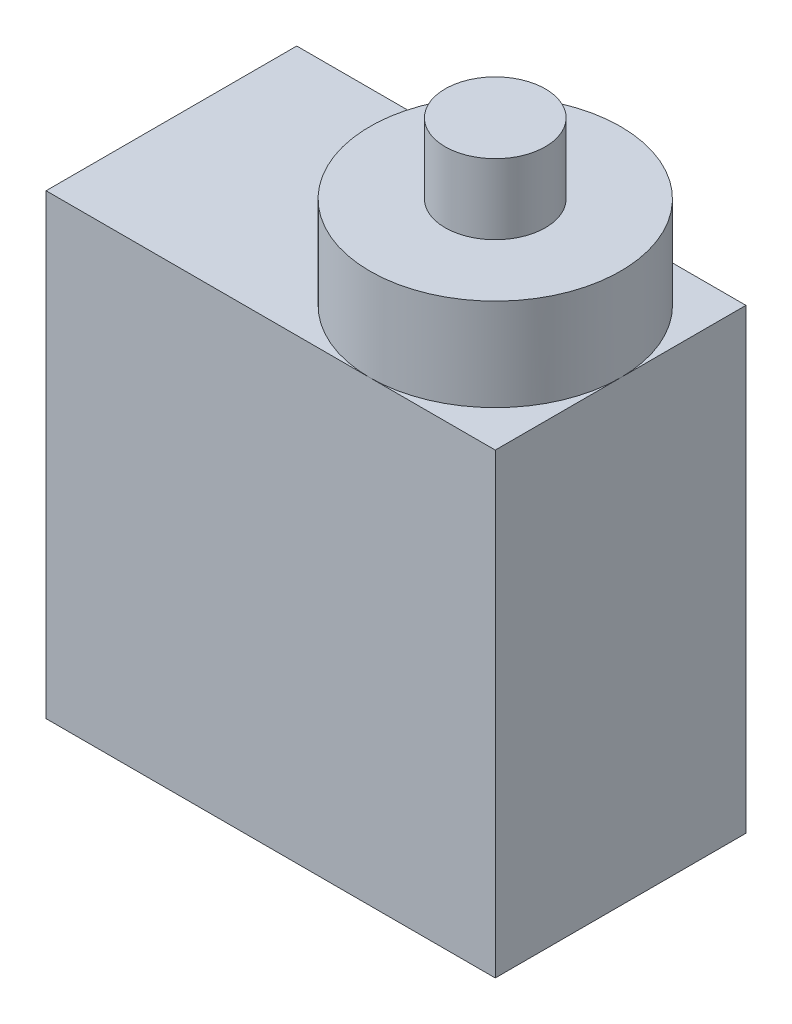
SolidWorks part; units mm, degrees
ref_plane "Front Plane" through (0, 0, 0) normal (0, 0, 1) x (1, 0, 0)
ref_plane "Top Plane" through (0, 0, 0) normal (0, 1, 0) x (1, 0, 0)
ref_plane "Right Plane" through (0, 0, 0) normal (1, 0, 0) x (0, 0, -1)
sketch "Sketch1" plane through (0, 0, 0) normal (0, 1, 0) x (1, 0, 0)
  line L1 (-11.2, 6.25) -> (11.2, 6.25)
  line L2 (-11.2, 6.25) -> (-11.2, -6.25)
  line L3 (-11.2, -6.25) -> (11.2, -6.25)
  line L4 (11.2, 6.25) -> (11.2, -6.25)
  line L5 (-11.2, 6.25) -> (11.2, -6.25) construction
  line L6 (-11.2, -6.25) -> (11.2, 6.25) construction
  point P0 (0, 0)
  dimension "D1" = 12.5
  dimension "D2" = 22.4
extrude "Boss-Extrude2" add sketch "Sketch1" along normal blind 11.4 and the other way blind 11.4 contours L1 L4 L3 L2
sketch "Sketch3" plane through (0, 11.4, 0) normal (0, 1, 0) x (1, 0, 0)
  line L0 (11.2, 6.25) -> (11.2, -6.25) construction
  circle A0 centre (4.95, 0) radius 6.25
  point P2 (0, 0)
  point P5 (11.2, 0)
  dimension "D1" = 6.25
extrude "Boss-Extrude3" add sketch "Sketch3" along normal blind 4.6
sketch "Sketch4" plane through (0, 16, 0) normal (0, 1, 0) x (1, 0, 0)
  circle A0 centre (4.95, 0) radius 2.5
  dimension "D1" = 5
extrude "Boss-Extrude4" add sketch "Sketch4" along normal blind 3.5
